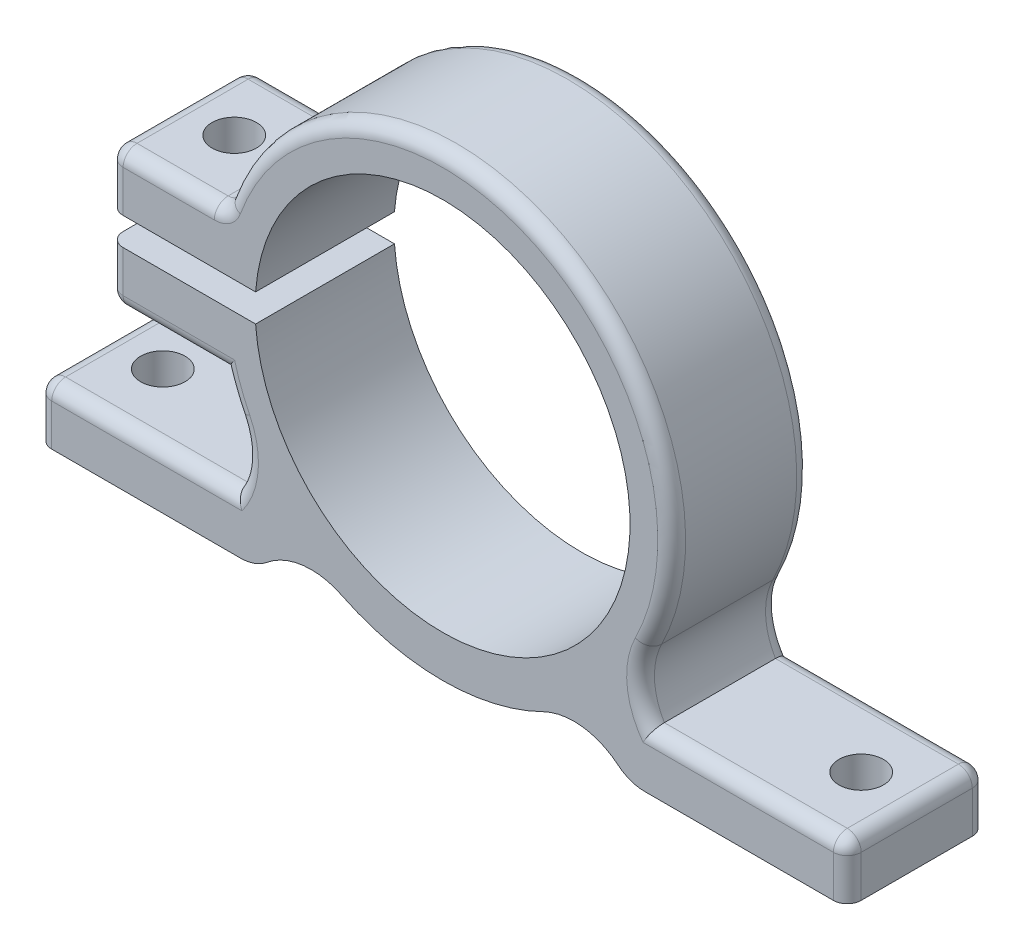
SolidWorks part; units mm, degrees
ref_plane "Front Plane" through (0, 0, 0) normal (0, 0, 1) x (1, 0, 0)
ref_plane "Top Plane" through (0, 0, 0) normal (0, 1, 0) x (1, 0, 0)
ref_plane "Right Plane" through (0, 0, 0) normal (1, 0, 0) x (0, 0, -1)
sketch "Sketch1" plane through (0, 0, 0) normal (0, 0, 1) x (1, 0, 0)
  line L0 (0, 0) -> (0, -50000) construction
  circle A1 centre (0, 0) radius 16.5
  dimension "D2" = 33
extrude "Boss-Extrude1" add sketch "Sketch1" along normal mid plane 10 contours A1
sketch "Sketch2" plane through (0, 0, 0) normal (0, 0, 1) x (1, 0, 0)
  line L0 (0, 0) -> (13.8492, -13.8492)
  line L1 (14.5563, -14.1421) -> (29.1421, -14.1421)
  line L2 (0, 0) -> (-13.8492, -13.8492)
  line L3 (-14.5563, -14.1421) -> (-29.1421, -14.1421)
  line L4 (0, 0) -> (0, -50000) construction
  arc A1 (13.8492, -13.8492) -> (14.5563, -14.1421) centre (14.5563, -13.1421) ccw
  arc A2 (-13.8492, -13.8492) -> (-14.5563, -14.1421) centre (-14.5563, -13.1421) cw
  point P12 (-14.1421, -14.1421)
  dimension "D5" = 1
  dimension "D1" = 15
  dimension "D2" = 45
  dimension "D3" = 20
  dimension "D4" = 45
extrude "Extrude-Thin1" add sketch "Sketch2" along normal mid plane 10 thin
sketch "Sketch4" plane through (0, 0, 0) normal (0, 0, 1) x (1, 0, 0)
  line L1 (-24, 5) -> (0, 5)
  line L2 (-24, 5) -> (-24, -5)
  line L3 (-24, -5) -> (0, -5)
  line L4 (0, 5) -> (0, -5)
  line L5 (-24, 5) -> (0, -5) construction
  line L6 (-24, -5) -> (0, 5) construction
  point P0 (-12, 0)
  dimension "D1" = 24
  dimension "D2" = 10
extrude "Boss-Extrude2" add sketch "Sketch4" along normal mid plane 10
sketch "Sketch5" plane through (0, 0, 5) normal (0, 0, 1) x (1, 0, 0)
  line L0 (-24, 5) -> (-24, -5) construction
  line L1 (-24, 1) -> (0, 1)
  line L2 (-24, 1) -> (-24, -1)
  line L3 (-24, -1) -> (0, -1)
  line L4 (0, 1) -> (0, -1)
  line L5 (-24, 1) -> (0, -1) construction
  line L6 (-24, -1) -> (0, 1) construction
  circle A0 centre (0, 0) radius 13.5
  point P6 (-12, 0)
  dimension "D1" = 27
  dimension "D2" = 2
extrude "Cut-Extrude1" cut sketch "Sketch5" against normal blind 26.5 contours A0 | L3 L4 L1 L2
sketch "Sketch6" plane through (0, 5, 0) normal (0, 1, 0) x (1, 0, 0)
  line L0 (-24, -5) -> (-24, 5) construction
  circle A0 centre (-20, 0) radius 1.6
  dimension "D1" = 3.2
  dimension "D2" = 4
extrude "Cut-Extrude2" cut sketch "Sketch6" against normal up to surface and the other way through all up to face at (-19.8621, -5, 0)
sketch "Sketch7" plane through (0, -12.1421, 0) normal (0, 1, 0) x (1, 0, 0)
  line L1 (-29.1421, -5) -> (-29.1421, 5) construction
  line L2 (29.1421, -5) -> (29.1421, 5) construction
  circle A0 centre (-25.1421, 0) radius 1.6
  circle A1 centre (25.1421, 0) radius 1.6
  dimension "D1" = 3.2
  dimension "D2" = 4
  dimension "D3" = 4
extrude "Cut-Extrude3" cut sketch "Sketch7" against normal through all
fillet "Fillet3" radius 5 4 edges at (12.9954, -10.167, 0) (10.167, -12.9954, 0) (-12.9954, -10.167, 0) (-10.167, -12.9954, 0)
fillet "Fillet1" radius 1 29 edges at (6.1884, 15.2955, 5) (6.1884, 15.2955, -5) (14.2592, -9.7661, -5) (14.2592, -9.7661, 5) (-14.2592, -9.7661, 5) (-14.2592, -9.7661, -5) (-29.1421, -14.1421, -5) (-22.0563, -12.1421, -5) (29.1421, -14.1421, 5) (22.0563, -12.1421, 5) (29.1421, -12.1421, 0) (-22.0563, -12.1421, 5) (-29.1421, -14.1421, 5) (-29.1421, -12.1421, 0) (22.0563, -12.1421, -5) (29.1421, -14.1421, -5) (-15.2955, -6.1884, -5) (-15.2955, -6.1884, 5) (-15.7242, 5, 0) (-19.8621, 5, -5) (-19.8621, -5, -5) (-24, -5, 0) (-24, 3, -5) (-24, 5, 0) (-19.8621, 5, 5) (-24, 3, 5) (-19.8621, -5, 5) (-24, -3, -5) (-24, -3, 5)
